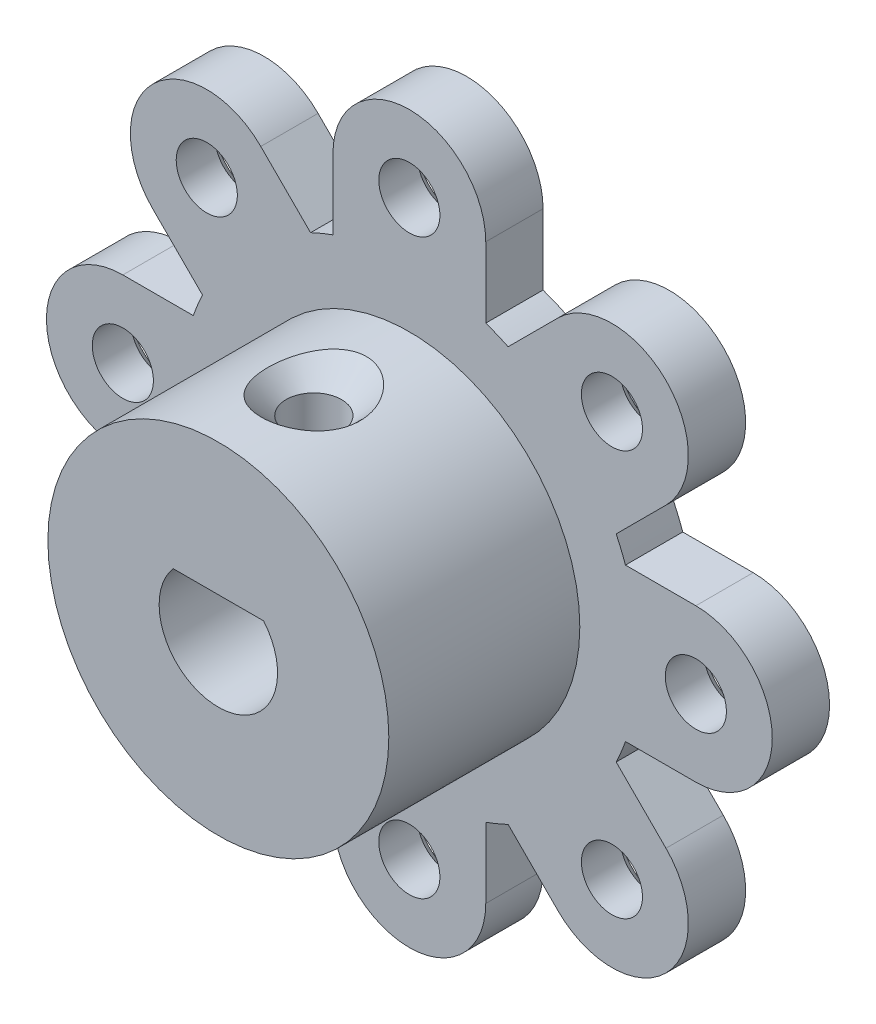
SolidWorks part; units mm, degrees
ref_plane "Front Plane" through (0, 0, 0) normal (0, 0, 1) x (1, 0, 0)
ref_plane "Top Plane" through (0, 0, 0) normal (0, 1, 0) x (1, 0, 0)
ref_plane "Right Plane" through (0, 0, 0) normal (1, 0, 0) x (0, 0, -1)
ref_axis "Axe1" through (0, 0, 11.8837) along (0, 0, -1)
sketch "Esquisse1" plane through (0, 0, 0) normal (0, 0, 1) x (1, 0, 0)
  line L0 (11.3137, 4) -> (15, 4)
  line L1 (11.3137, -4) -> (15, -4)
  line L2 (0, 0) -> (11.0866, 4.5922)
  line L3 (0, 0) -> (11.0866, -4.5922)
  line L4 (0, 0) -> (15, 0) construction
  arc A0 (11.0866, 4.5922) -> (11.3137, 4) centre (0, 0) cw
  arc A1 (11.0866, -4.5922) -> (11.3137, -4) centre (0, 0) ccw
  arc A2 (15, -4) -> (15, 4) centre (15, 0) ccw
  dimension "D1" = 12
  dimension "D2" = 8
  dimension "D3" = 15
  dimension "D4" = 22.5
  dimension "D5" = 22.5
extrude "Main" add sketch "Esquisse1" along normal blind 3
pattern_circular "Répétition circulaire1" count 8 every 45 about axis through (0, 0, 11.8837) along (0, 0, -1) of "Main"
sketch "Esquisse2" plane through (0, 0, 3) normal (0, 0, 1) x (1, 0, 0)
  circle A0 centre (0, 0) radius 3.1
  circle A1 centre (0, 0) radius 8.925
  dimension "D1" = 6.2
  dimension "D2" = 17.85
extrude "MotorLink" add sketch "Esquisse2" along normal blind 10
sketch "Esquisse3" plane through (0, 0, 3) normal (0, 0, 1) x (1, 0, 0)
  line L0 (-2.3685, 2) -> (2.3685, 2)
  circle A0 centre (0, 0) radius 3.1 construction
  arc A1 (2.3685, 2) -> (-2.3685, 2) centre (0, 0) ccw
  dimension "D1" = 2
extrude "Meplat" add sketch "Esquisse3" along normal blind 10
sketch "Esquisse4" plane through (0, 0, 3) normal (0, 0, 1) x (1, 0, 0)
  circle A0 centre (0, 0) radius 3.1
  circle A1 centre (0, 0) radius 3.1 construction
extrude "Hole" cut sketch "Esquisse4" against normal through all
sketch "Esquisse5" plane through (0, 0, 0) normal (0, 0, -1) x (-1, 0, 0)
  circle A0 centre (0, 0) radius 3.1
  circle A1 centre (0, 0) radius 4
  circle A2 centre (0, 0) radius 3.1 construction
  dimension "D1" = 8
extrude "RollingBearingLink" add sketch "Esquisse5" along normal blind 7
sketch "Esquisse6" plane through (0, 0, 0) normal (0, 0, -1) x (-1, 0, 0)
  circle A0 centre (0, 0) radius 5
  circle A1 centre (0, 0) radius 4
  circle A2 centre (0, 0) radius 4 construction
  dimension "D1" = 10
extrude "RollingBearLink2" add sketch "Esquisse6" along normal blind 0.5
hole_wizard "Fraisage pour vis à tête fraisée (100) #01" positions "Esquisse9" profile "Esquisse10" countersink size "#0" standard "Ansi Inch" end condition through all
sketch "Esquisse9" plane through (0, 0, 0) normal (0, 0, -1) x (-1, 0, 0)
  arc A1 (15, -4) -> (15, 4) centre (15, 0) ccw construction
  point P0 (15, 0)
sketch "Esquisse10" plane through (-15, 0, 0) normal (1, 0, 0) x (0, 1, 0)
  line L0 (0, 0) -> (0, 13)
  line L1 (0, 13) -> (1.6, 13)
  line L2 (1.6, 13) -> (1.6, 0.965)
  line L3 (1.6, 0.965) -> (2.75, 0)
  line L5 (2.75, 0) -> (0, 0)
  line L6 (-1.6, 0.965) -> (-2.75, 0) construction
  line L11 (0, -6.35) -> (0, 107.95) construction
  dimension "Diamètre du perçage jusqu'au prochain" = 3.2
  dimension "Profondeur du perçage jusqu'au prochain" = 13
  dimension "Diamètre du fraisage entrant" = 5.5
  dimension "Angle du fraisage entrant" = 100
pattern_circular "Répétition circulaire2" count 8 every 45 about axis through (0, 0, 11.8837) along (0, 0, -1) of "Fraisage pour vis à tête fraisée (100) #01"
ref_plane "Plane1" through (0, 8.925, 0) normal (0, 1, 0) x (1, 0, 0)
hole_wizard "CSK for M2.5 Flat Head Machine Screw1" positions "Sketch3" profile "Sketch2" countersink size "M2.5" standard "ANSI Metric" end condition through all
sketch "Sketch3" plane through (0, 8.925, 0) normal (0, 1, 0) x (1, 0, 0)
  line L0 (0, -11.8837) -> (0, 8.879) construction
  line L1 (-8.925, -13) -> (8.925, -13) construction
  point P0 (0, -8)
  dimension "D1" = 5
sketch "Sketch2" plane through (0, 8.925, 8) normal (1, 0, 0) x (0, 0, 1)
  line L0 (0, 0) -> (0, 27.925)
  line L1 (0, 27.925) -> (1.45, 27.925)
  line L2 (1.45, 27.925) -> (1.45, 1.3)
  line L3 (1.45, 1.3) -> (2.75, 0)
  line L5 (2.75, 0) -> (0, 0)
  line L6 (-1.45, 1.3) -> (-2.75, 0) construction
  line L11 (0, -6.35) -> (0, 107.95) construction
  dimension "Thru Hole Dia." = 2.9
  dimension "Thru Hole Depth" = 27.925
  dimension "Near C'Sink Dia." = 5.5
  dimension "Near C'Sink Angle" = 90
